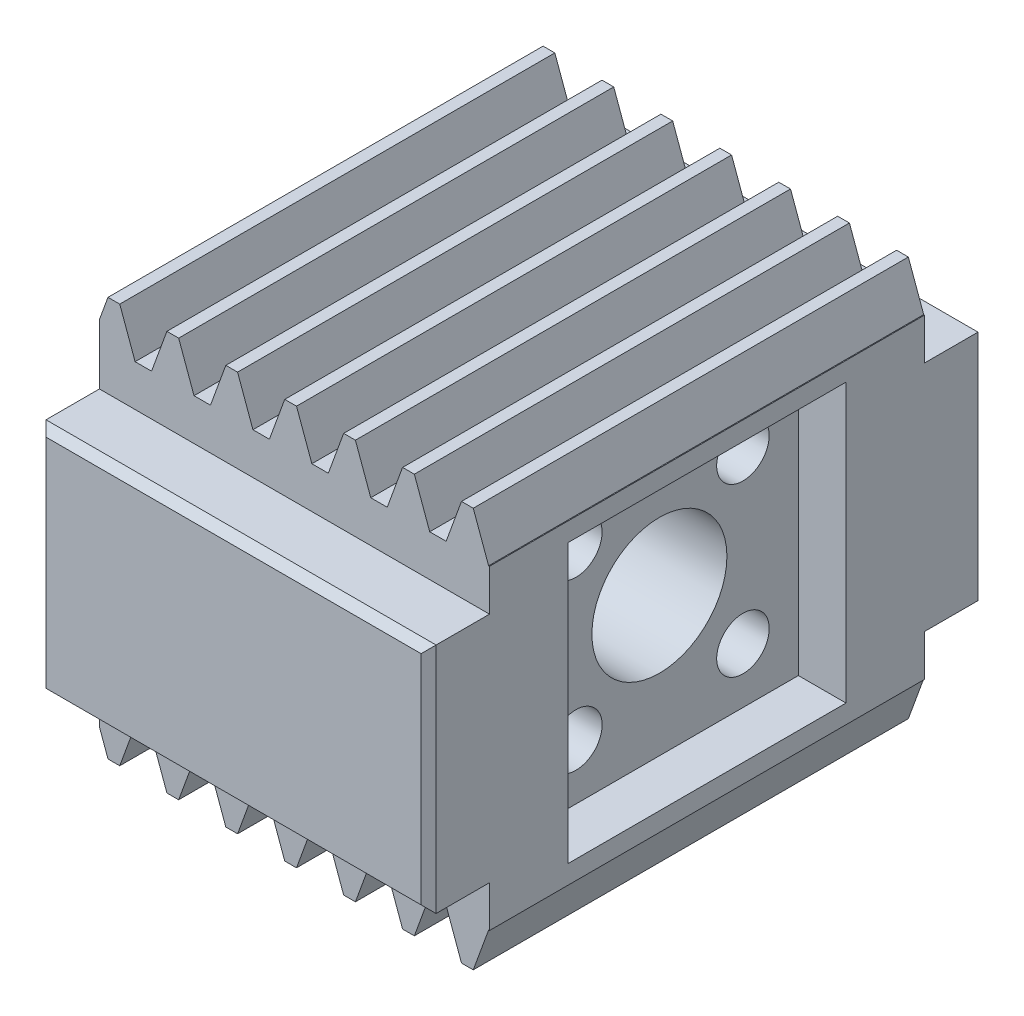
SolidWorks part; units mm, degrees
extrude "Blank" add sketch "BlankSke" against normal blind 29
sketch "BlankSke" plane through (0, 0, 0) normal (0, 0, 1) x (1, 0, 0)
  line L1 (0, 0) -> (27, 0)
  line L2 (0, 0) -> (0, 13.325)
  line L3 (0, 13.325) -> (27, 13.325)
  line L4 (27, 0) -> (27, 13.325)
  dimension "Length" = 27
ref_plane "Plane1" through (0, 0, 0) normal (0, 0, 1) x (1, 0, 0)
ref_plane "Plane2" through (0, 0, 0) normal (0, 1, 0) x (1, 0, 0)
ref_plane "Plane3" through (0, 0, 0) normal (1, 0, 0) x (0, 0, -1)
sketch "HoldingSke" plane through (0, 0, 0) normal (0, 1, 0) x (1, 0, 0)
  line L0 (0, 0) -> (0.1113, 0.7922)
  line L1 (-15, 0) -> (100, 0) construction
  line L2 (0, 0) -> (-2.1039, 2.3779)
  line L3 (0, 0) -> (-11.863, 4.5341)
  line L4 (0, 0) -> (8.552, 1.2019)
  line L5 (0, 0) -> (-23.7986, -8.8762)
  line L6 (0, 0) -> (-10.5278, -7.1032)
  line L9 (-71.009, 38.7566) -> (-45.6373, 47.9912)
  line L10 (-76.2, 3.6279) -> (-64.125, 3.6279)
  line L11 (0, 0) -> (-29, 0)
  line L12 (-76.2, 101.6) -> (-76.155, 101.6)
  line L13 (24.9733, 27.94) -> (52.9518, 28.4284)
  line L14 (24.9733, 27.94) -> (24.9743, 27.94)
  line L15 (24.9733, 27.94) -> (100.4006, 29.5858)
  circle A0 centre (0, 0) radius 19.05
  circle A1 centre (0, 0) radius 6.0375
  circle A2 centre (0, 0) radius 12.7
  dimension "Num_teeth" = 8
  dimension "Width" = 29
  dimension "Length" = 27
  dimension "Pitch_height" = 12.075
sketch "TooCutSkeIll" plane through (0, 0, 0) normal (0, 0, 1) x (1, 0, 0)
  line L0 (-1.5597, 13.2921) -> (-0.6231, 10.7188)
  line L1 (-0.3285, 10.5125) -> (0.3285, 10.5125)
  line L2 (0.6231, 10.7188) -> (1.5597, 13.2921)
  line L3 (27, 13.325) -> (0, 13.325) construction
  line L4 (0, 0) -> (0, 64.897) construction
  line L5 (-13.208, 12.075) -> (12.954, 12.075) construction
  line L6 (0, 0) -> (27, 0) construction
  line L7 (1.1167, 12.075) -> (1.1167, 48.7463) construction
  line L8 (-1.1167, 12.075) -> (-1.1167, 48.7463) construction
  line L9 (1.6067, 13.325) -> (1.6067, 13.3504)
  line L10 (-1.6067, 13.325) -> (-1.6067, 13.3504)
  line L11 (-1.6067, 13.3504) -> (1.6067, 13.3504)
  arc A0 (0.3285, 10.5125) -> (0.6231, 10.7188) centre (0.3285, 10.826) ccw
  arc A1 (-0.6231, 10.7188) -> (-0.3285, 10.5125) centre (-0.3285, 10.826) ccw
  arc A2 (1.6067, 13.325) -> (1.5597, 13.2921) centre (1.6067, 13.275) ccw
  arc A3 (-1.5597, 13.2921) -> (-1.6067, 13.325) centre (-1.6067, 13.275) ccw
  dimension "Addendum_plus" = 1.2754
  dimension "Pitch_height" = 12.075
  dimension "Pressure_angle" = 20
  dimension "Gap_width" = 2.2335
  dimension "Dedendum" = 1.5625
extrude "ToothCutIll" [suppressed] cut sketch "TooCutSkeIll" against normal through all
sketch "TooCutSkeSim" plane through (0, 0, 0) normal (0, 0, 1) x (1, 0, 0)
  line L0 (0.548, 10.5125) -> (-0.548, 10.5125)
  line L1 (1.581, 13.3504) -> (0.548, 10.5125)
  line L2 (0, 17.4625) -> (0, 53.467) construction
  line L3 (1.581, 13.3504) -> (-1.581, 13.3504)
  line L6 (-1.581, 13.3504) -> (-0.548, 10.5125)
  line L9 (-1.1167, 12.075) -> (1.1167, 12.075) construction
  line L10 (0, 0) -> (27, 0) construction
  line L11 (1.1167, 12.075) -> (1.1167, 53.467) construction
  line L12 (-1.1167, 12.075) -> (-1.1167, 53.467) construction
  dimension "Addendum_plus" = 1.2754
  dimension "Pitch_height" = 12.075
  dimension "Pressure_angle" = 20
  dimension "Gap_width" = 2.2335
  dimension "Dedendum" = 1.5625
extrude "ToothCutSim" cut sketch "TooCutSkeSim" against normal through all
pattern_linear "TeethCuts" count 8 spacing 3.927 along (1, 0, 0) of "ToothCutIll", "ToothCutSim"
sketch "Sketch2" plane through (0, 0, 0) normal (-1, 0, 0) x (0, 0, 1)
  line L0 (-29, 0) -> (0, 0) construction
  line L1 (-7.445, 8.763) -> (-21.555, 8.763)
  line L4 (-3.25, 0) -> (-25.75, 0)
  arc A0 (-21.555, 8.763) -> (-25.75, 0) centre (-14.5, 0) ccw
  arc A1 (-3.25, 0) -> (-7.445, 8.763) centre (-14.5, 0) ccw
  dimension "D1" = 8.763
  dimension "D2" = 22.5
extrude "Cut-Extrude1" cut sketch "Sketch2" against normal blind 6.75
sketch "Sketch3" plane through (6.75, 0, 0) normal (-1, 0, 0) x (0, 0, 1)
  line L0 (-3.25, 0) -> (-25.75, 0) construction
  circle A0 centre (-14.5, 0) radius 5.25
extrude "Cut-Extrude2" cut sketch "Sketch3" against normal blind 10.25
sketch "Sketch4" plane through (17, 0, 0) normal (-1, 0, 0) x (0, 0, 1)
  line L0 (-9.25, 0) -> (-19.75, 0) construction
  circle A0 centre (-14.5, 0) radius 4.5
extrude "Cut-Extrude3" cut sketch "Sketch4" against normal through all both and the other way through all
sketch "Sketch5" plane through (27, 0, 0) normal (1, 0, 0) x (0, 0, -1)
  circle A0 centre (14.5, 0) radius 7.874 construction
  circle A1 centre (8.9322, 5.5678) radius 2.5
  circle A2 centre (20.0678, 5.5678) radius 2.5
extrude "Cut-Extrude4" cut sketch "Sketch5" against normal blind 3.175
sketch "Sketch6" plane through (23.825, 0, 0) normal (1, 0, 0) x (0, 0, -1)
  circle A0 centre (20.0678, 5.5678) radius 1.75
  circle A1 centre (8.9322, 5.5678) radius 1.75
extrude "Cut-Extrude5" cut sketch "Sketch6" against normal through all
mirror "Mirror1" about plane through (0, 0, -29) normal (0, -1, 0) of "Cut-Extrude2", "Cut-Extrude3", "Cut-Extrude1", "TeethCuts", "ToothCutSim", "Blank", "Cut-Extrude5", "Cut-Extrude4"
ref_plane "Plane4" through (0, 0, -14.5) normal (0, 0, 1) x (1, 0, 0)
sketch "Sketch7" plane through (0, 0, -14.5) normal (0, 0, 1) x (1, 0, 0)
  line L0 (0, 10.5125) -> (0, -10.5125) construction
  line L2 (0, -12.075) -> (27.3762, -12.075)
  point P3 (0, 0)
  dimension "D1" = 12.075
sketch "Sketch8" plane through (0, 0, -14.5) normal (0, 0, 1) x (1, 0, 0)
  line L0 (27.2819, 12.075) -> (0, 12.075)
  line L2 (0, 10.5125) -> (0, -10.5125) construction
  point P6 (0, 0)
  dimension "D1" = 12.075
sketch "Sketch9" plane through (27, 0, 0) normal (1, 0, 0) x (0, 0, -1)
  line L0 (7.445, 8.763) -> (21.555, 8.763) construction
  line L1 (5.737, -8.763) -> (23.263, -8.763)
  line L2 (5.737, -8.763) -> (5.737, 8.763)
  line L3 (5.737, 8.763) -> (23.263, 8.763)
  line L4 (23.263, -8.763) -> (23.263, 8.763)
  line L5 (5.737, -8.763) -> (23.263, 8.763) construction
  line L6 (5.737, 8.763) -> (23.263, -8.763) construction
  line L7 (7.445, 8.763) -> (21.555, 8.763)
  line L8 (23.763, -9.263) -> (23.763, 9.263)
  line L9 (5.237, 9.263) -> (23.763, 9.263)
  line L10 (5.237, -9.263) -> (5.237, 9.263)
  line L11 (5.237, -9.263) -> (23.763, -9.263)
  circle A0 centre (20.0678, 5.5678) radius 1.25
  circle A1 centre (20.0678, -5.5678) radius 1.25
  circle A2 centre (8.9322, 5.5678) radius 1.25
  circle A3 centre (8.9322, -5.5678) radius 1.25
  point P12 (14.5, 0)
  dimension "D1" = 2.5
  dimension "D2" = 3.1952
  dimension "D3" = 3.1952
extrude "Cut-Extrude6" cut sketch "Sketch9" against normal blind 3.175 contours L8 L9 L10 L11
sketch "Sketch10" plane through (27, 0, 0) normal (1, 0, 0) x (0, 0, -1)
  line L0 (0, -10.5125) -> (0, 10.5125) construction
  line L2 (0, -10.5125) -> (0, 10.5125)
  line L3 (29, 13.325) -> (0, 13.325) construction
  line L4 (0, -13.325) -> (29, -13.325) construction
  line L5 (29, 13.325) -> (0, 13.325)
  line L6 (0, -13.325) -> (29, -13.325)
  line L7 (0, -7.75) -> (-4.06, -7.75)
  line L8 (-4.06, -7.75) -> (-4.06, 7.75)
  line L9 (-4.06, 7.75) -> (0, 7.75)
  line L10 (14.5, 0) -> (14.5, 3.4435) construction
  line L11 (33.06, 7.75) -> (29, 7.75)
  line L12 (33.06, -7.75) -> (33.06, 7.75)
  line L13 (29, -7.75) -> (33.06, -7.75)
  line L14 (29, -10.5125) -> (29, 10.5125) construction
  line L15 (29, -10.5125) -> (29, 10.5125)
  point P8 (-4.06, 0)
  point P11 (-4.06, 0)
  point P13 (0, 0)
  line M12 (29, -10.5125) -> (29, 10.5125)
  dimension "D1" = 15.5
  dimension "D2" = 4.06
extrude "Boss-Extrude2" add sketch "Sketch10" against normal through all contours L13 L12 L11 M12 | L9 L8 L7 L2 region at (27, 0, 2.03) region at (27, 0, -31.03)
sketch "Sketch12" plane through (0, 0, 0) normal (-1, 0, 0) x (0, 0, 1)
  line L1 (0, 10.5125) -> (-29, 10.5125)
  line L2 (-21.555, -8.763) -> (-7.445, -8.763)
  line L3 (-7.445, 8.763) -> (-21.555, 8.763)
  line L4 (-21.555, -8.763) -> (-7.445, -8.763)
  line L5 (-7.445, 8.763) -> (-21.555, 8.763)
  line L6 (0, 10.5125) -> (0, 16.7258)
  line L7 (0, 16.7258) -> (-29, 16.7258)
  line L8 (-29, 10.5125) -> (-29, 16.7258)
  line L9 (0, -10.5125) -> (-29, -10.5125)
  line L10 (0, -10.5125) -> (0, -15.5788)
  line L11 (0, -15.5788) -> (-29, -15.5788)
  line L12 (-29, 10.5125) -> (-29, 7.75)
  line L13 (-29, 7.75) -> (-33.06, 7.75)
  line L14 (-33.06, 7.75) -> (-33.06, -7.75)
  line L15 (-33.06, -7.75) -> (-29, -7.75)
  line L16 (-29, -7.75) -> (-29, -10.5125)
  line L17 (-29, -10.5125) -> (0, -10.5125)
  line L18 (0, -10.5125) -> (0, -7.75)
  line L19 (0, -7.75) -> (4.06, -7.75)
  line L20 (4.06, -7.75) -> (4.06, 7.75)
  line L21 (4.06, 7.75) -> (0, 7.75)
  line L22 (0, 7.75) -> (0, 10.5125)
  line L23 (0, 10.5125) -> (-29, 10.5125)
  line L24 (-29, 10.5125) -> (-29, 7.75)
  line L25 (-29, 7.75) -> (-33.06, 7.75)
  line L26 (-33.06, 7.75) -> (-33.06, -7.75)
  line L27 (-33.06, -7.75) -> (-29, -7.75)
  line L28 (-29, -7.75) -> (-29, -10.5125)
  line L29 (-29, -10.5125) -> (0, -10.5125)
  line L30 (0, -10.5125) -> (0, -7.75)
  line L31 (0, -7.75) -> (4.06, -7.75)
  line L32 (4.06, -7.75) -> (4.06, 7.75)
  line L33 (4.06, 7.75) -> (0, 7.75)
  line L34 (0, 7.75) -> (0, 10.5125)
  line L35 (0, 10.5125) -> (-29, 10.5125)
  line L36 (-29, -10.5125) -> (-29, -15.5788)
  circle A0 centre (-20.0678, 5.5678) radius 1.75 construction
  circle A1 centre (-8.9322, 5.5678) radius 1.75 construction
  arc A2 (-7.445, -8.763) -> (-7.445, 8.763) centre (-14.5, 0) ccw
  arc A3 (-21.555, 8.763) -> (-21.555, -8.763) centre (-14.5, 0) ccw
  arc A4 (-7.445, -8.763) -> (-7.445, 8.763) centre (-14.5, 0) ccw
  arc A5 (-21.555, 8.763) -> (-21.555, -8.763) centre (-14.5, 0) ccw
  circle A6 centre (-8.9322, -5.5678) radius 1.75 construction
  circle A7 centre (-20.0678, -5.5678) radius 1.75 construction
  circle A8 centre (-20.0678, 5.5678) radius 1.75
  circle A9 centre (-8.9322, 5.5678) radius 1.75
  circle A10 centre (-8.9322, -5.5678) radius 1.75
  circle A11 centre (-20.0678, -5.5678) radius 1.75
  circle A12 centre (-14.5, 0) radius 5.25 construction
  circle A13 centre (-14.5, 0) radius 5.25
  line M17 (-29, 10.5125) -> (-29, 7.75)
  line M18 (-29, 7.75) -> (-33.06, 7.75)
  line M19 (-33.06, 7.75) -> (-33.06, -7.75)
  line M20 (-33.06, -7.75) -> (-29, -7.75)
  line M21 (-29, -7.75) -> (-29, -10.5125)
  line M22 (-29, -10.5125) -> (0, -10.5125)
  line M23 (0, -10.5125) -> (0, -7.75)
  line M24 (0, -7.75) -> (4.06, -7.75)
  line M25 (4.06, -7.75) -> (4.06, 7.75)
  line M26 (4.06, 7.75) -> (0, 7.75)
  line M27 (0, 7.75) -> (0, 10.5125)
  line M28 (0, 10.5125) -> (-29, 10.5125)
  arc M29 (-7.445, 8.763) -> (-7.445, -8.763) centre (-14.5, 0) cw
  line M30 (-7.445, -8.763) -> (-21.555, -8.763)
  arc M31 (-21.555, -8.763) -> (-21.555, 8.763) centre (-14.5, 0) cw
  line M32 (-21.555, 8.763) -> (-7.445, 8.763)
  dimension "D1" = 0
  dimension "D2" = 0
extrude "Cut-Extrude7" cut sketch "Sketch12" against normal offset from surface (1 mm away) 26 contours L8 L6 L7 M28 | M28 M17 M18 M19 M20 M21 M22 M23 M24 M25 M26 M27 M32 M29 M30 M31 | L36 L11 L10 M22 region at (0, 9.1313, -0.4266) region at (0, 13.6192, -14.5) region at (0, -13.0457, -14.5) up to face at (27, 0, -14.5)
extrude "Cut-Extrude8" cut sketch "Sketch12<10>" against normal offset from surface (7.75 mm away) 6.75 contours A13 A11 A10 A9 A8 M29 M32 M31 M30 region at (0, 0, -25.4648) up to face at (1, 0, -14.5)
sketch "Sketch12<10>" plane through (0, 0, 0) normal (-1, 0, 0) x (0, 0, 1) same geometry as "Sketch12"
extrude "Cut-Extrude9" cut sketch "Sketch12<11>" against normal blind 0.75 from surface contours A13 A11 A10 A9 A8 M29 M32 M31 M30 region at (0, 0, -25.4648) starting at face at (7.75, 5.5678, -10.6822)
sketch "Sketch12<11>" plane through (0, 0, 0) normal (-1, 0, 0) x (0, 0, 1) same geometry as "Sketch12"
chamfer "Chamfer1" distance 0.5 angle 45 8 edges at (14, 7.75, -33.06) (14, -7.75, -33.06) (14, 7.75, 4.06) (14, -7.75, 4.06) (27, 0, -33.06) (27, 0, 4.06) (1, 0, 4.06) (1, 0, -33.06)
equation "' \"Module@HoldingSke\" = 6.35"
equation "' \"Num_teeth@HoldingSke\" = 12"
equation "' \"Ap@HoldingSke\" =  20"
equation "' \"Ap@HoldingSke\" = 20"
equation "' \"Width@HoldingSke\" = 0.25 * 25.4"
equation "' \"Show_teeth@HoldingSke\" = 500"
equation "' \"Backlash@HoldingSke\" = 0.009 * 25.4"
equation "' \"Addendum_fac@HoldingSke\" = 1.0"
equation "' \"Dedendum_fac@HoldingSke\" = 1.25"
equation "' \"Dedendum_add@HoldingSke\" = 0.00005 * 25.4"
equation "' \"Clearance_fac@HoldingSke\" = 0.25"
equation "' \"Pitch_height@HoldingSke\" = 1 * 25.4"
equation "' \"Length@HoldingSke\" = 4.71 * 25.4"
equation "\"Pitch@HoldingSke\" = 1 / \"Module@HoldingSke\""
equation "\"MPH@HoldingSke\" = \"Dedendum_fac@HoldingSke\" / \"Pitch@HoldingSke\" + 2 * \"Dedendum_add@HoldingSke\" + 0.002 * 25.4"
equation "\"MPH@HoldingSke\" = ((sgn( \"MPH@HoldingSke\" - \"Pitch_height@HoldingSke\")+1)*( \"MPH@HoldingSke\" - \"Pitch_height@HoldingSke\"))/2 + \"Pitch_height@HoldingSke\""
equation "\"Blank_height@BlankSke\" = \"Pitch_height@HoldingSke\" + \"Addendum_fac@HoldingSke\"  / \"Pitch@HoldingSke\" "
equation "\"Length@BlankSke\" =  \"Length@HoldingSke\""
equation "\"Face_width@Blank\" = \"Width@HoldingSke\""
equation "\"Pressure_angle@TooCutSkeIll\" = \"Ap@HoldingSke\""
equation "\"Addendum_plus@TooCutSkeIll\" =  \"Addendum_fac@HoldingSke\"  / \"Pitch@HoldingSke\" + 0.001 *25.4"
equation "\"Dedendum@TooCutSkeIll\" = \"Dedendum_fac@HoldingSke\"  / \"Pitch@HoldingSke\""
equation "\"Pitch_height@TooCutSkeIll\" =  \"MPH@HoldingSke\""
equation "\"Gap_width@TooCutSkeIll\" = 3.14159265 / 2 / \"Pitch@HoldingSke\" + 6 * \"Backlash@HoldingSke\""
equation "\"Pressure_angle@TooCutSkeSim\" = \"Ap@HoldingSke\""
equation "\"Addendum_plus@TooCutSkeSim\" =  \"Addendum_fac@HoldingSke\"  / \"Pitch@HoldingSke\" + 0.001 * 25.4"
equation "\"Dedendum@TooCutSkeSim\" = \"Dedendum_fac@HoldingSke\"  / \"Pitch@HoldingSke\""
equation "\"Pitch_height@TooCutSkeSim\" =  \"MPH@HoldingSke\""
equation "\"Gap_width@TooCutSkeSim\" = 3.14159265 / 2 / \"Pitch@HoldingSke\" + 6 * \"Backlash@HoldingSke\""
equation "\"Root_fillet@TooCutSkeIll\" = \"Clearance_fac@HoldingSke\" / \"Pitch@HoldingSke\" + \"Dedendum_add@HoldingSke\""
equation "\"Break_rad@TooCutSkeIll\" = 0.02 / \"Pitch@HoldingSke\" * 2"
equation "\"Linear_pitch@TeethCuts\" = 3.14159265 / \"Pitch@HoldingSke\""
equation "\"Num_teeth@HoldingSke\" = int( ( \"Length@HoldingSke\" + 0 ) / (3.14159265 / \"Pitch@HoldingSke\")) + 0.9999  + 1"
equation " \"Num_teeth@TeethCuts\" = int( \"Show_teeth@HoldingSke\" ) + 1"
equation " \"Num_teeth@TeethCuts\" = ((sgn( \"Num_teeth@TeethCuts\" - \"Num_teeth@HoldingSke\" )-1)*( \"Num_teeth@TeethCuts\" - \"Num_teeth@HoldingSke\" ))/-2+ \"Num_teeth@HoldingSke\""
equation " \"Num_teeth@TeethCuts\" = ((sgn( \"Num_teeth@TeethCuts\" - 2.0)+1)*( \"Num_teeth@TeethCuts\" - 2.0))/2 +2.0"
equation "\"D3@Sketch9\"=\"D2@Sketch9\""
